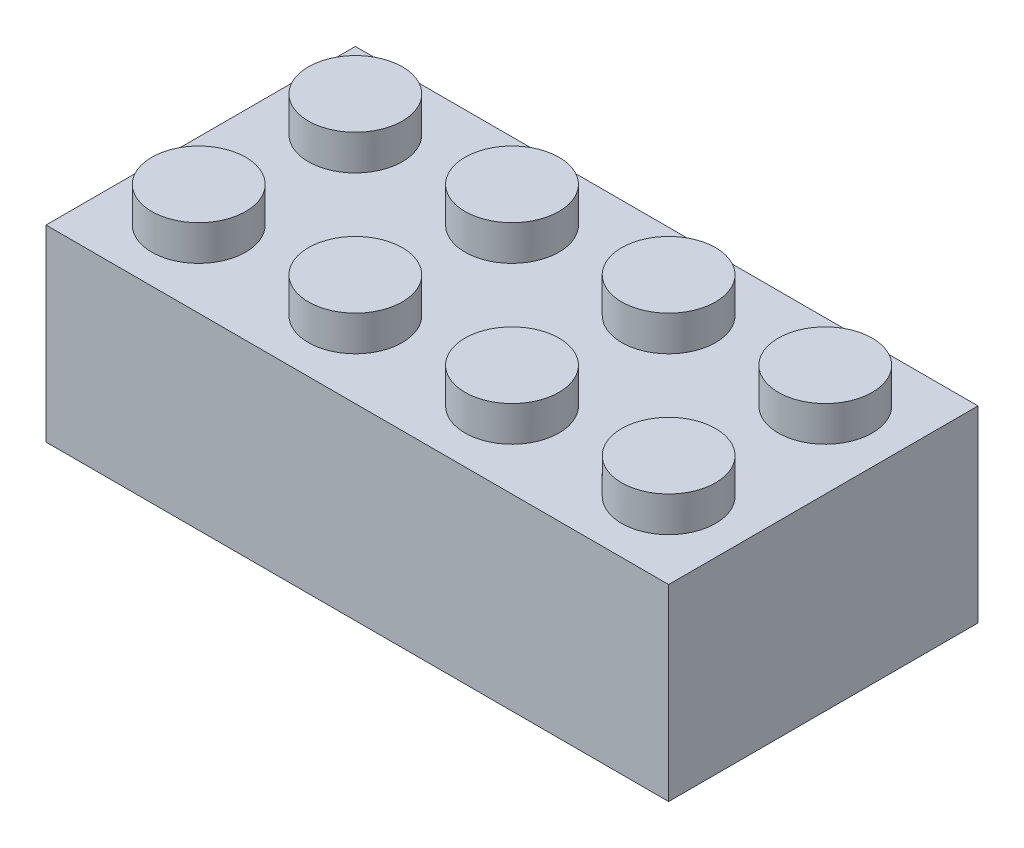
SolidWorks part; units mm, degrees
ref_plane "Front Plane" through (0, 0, 0) normal (0, 0, 1) x (1, 0, 0)
ref_plane "Top Plane" through (0, 0, 0) normal (0, 1, 0) x (1, 0, 0)
ref_plane "Right Plane" through (0, 0, 0) normal (1, 0, 0) x (0, 0, -1)
sketch "Sketch1" plane through (0, 0, 0) normal (0, 1, 0) x (1, 0, 0)
  line L1 (-15.9, -7.9) -> (15.9, -7.9)
  line L2 (-15.9, -7.9) -> (-15.9, 7.9)
  line L3 (-15.9, 7.9) -> (15.9, 7.9)
  line L4 (15.9, -7.9) -> (15.9, 7.9)
  line L5 (-15.9, -7.9) -> (15.9, 7.9) construction
  line L6 (-15.9, 7.9) -> (15.9, -7.9) construction
  point P0 (0, 0)
  dimension "D1" = 31.8
  dimension "D2" = 15.8
extrude "Boss-Extrude1" add sketch "Sketch1" along normal blind 9.6
sketch "Sketch2" plane through (0, 0, 0) normal (0, -1, 0) x (1, 0, 0)
  line L0 (-15.9, 7.9) -> (15.9, 7.9) construction
  line L1 (-14.5, -6.7) -> (14.5, -6.7)
  line L2 (-14.5, -6.7) -> (-14.5, 6.7)
  line L3 (-14.5, 6.7) -> (14.5, 6.7)
  line L4 (14.5, -6.7) -> (14.5, 6.7)
  line L5 (-14.5, -6.7) -> (14.5, 6.7) construction
  line L6 (-14.5, 6.7) -> (14.5, -6.7) construction
  line L7 (-15.9, -7.9) -> (-15.9, 7.9) construction
  point P0 (0, 0)
  dimension "D1" = 1.2
  dimension "D2" = 1.4
extrude "Cut-Extrude1" cut sketch "Sketch2" against normal offset from surface (8.6 mm away) 1 up to face at (0, 9.6, 0)
sketch "Sketch3" plane through (0, 8.6, 0) normal (0, -1, 0) x (1, 0, 0)
  line L0 (0, 0) -> (-14.5, 0) construction
  line L1 (-14.5, -6.7) -> (-14.5, 6.7) construction
  line L2 (0, 0) -> (0, 6.7) construction
  line L3 (-14.5, 6.7) -> (14.5, 6.7) construction
  line L4 (-14.5, 4) -> (0, 4) construction
  line L5 (-4, 6.7) -> (-4, 0) construction
  line L6 (-12, 6.7) -> (-12, 0) construction
  circle A0 centre (-12, 4) radius 2.4
  circle A1 centre (-4, 4) radius 2.4
  circle A2 centre (-12, 4) radius 1.3
  circle A3 centre (-4, 4) radius 1.3
  circle A4 centre (4, 4) radius 1.3
  circle A5 centre (12, 4) radius 1.3
  circle A6 centre (4, 4) radius 2.4
  circle A7 centre (12, 4) radius 2.4
  circle A8 centre (12, -4) radius 2.4
  circle A9 centre (4, -4) radius 2.4
  circle A10 centre (12, -4) radius 1.3
  circle A11 centre (4, -4) radius 1.3
  circle A12 centre (-4, -4) radius 1.3
  circle A13 centre (-12, -4) radius 1.3
  circle A14 centre (-4, -4) radius 2.4
  circle A15 centre (-12, -4) radius 2.4
  dimension "D4" = 4.8
  dimension "D5" = 4.8
  dimension "D6" = 1.1
  dimension "D7" = 1.1
  dimension "D1" = 4
  dimension "D2" = 12
  dimension "D3" = 4
extrude "Boss-Extrude2" add sketch "Sketch3" against normal blind 2.8 contours A15 | A14 | A0 | A1 | A6 | A9 | A7 | A8
extrude "Cut-Extrude2" cut sketch "Sketch3<3>" against normal offset from surface (1.7 mm away) 1.1 contours A13 | A2 | A3 | A12 | A4 | A11 | A10 | A5 up to face at (-12, 11.4, 1.6)
sketch "Sketch3<3>" plane through (0, 8.6, 0) normal (0, -1, 0) x (1, 0, 0) same geometry as "Sketch3"
sketch "Sketch4" plane through (0, 8.6, 0) normal (0, -1, 0) x (1, 0, 0)
  line L0 (-14.5, 0) -> (14.5, 0) construction
  line L1 (-14.5, -6.7) -> (-14.5, 6.7) construction
  line L2 (14.5, -6.7) -> (14.5, 6.7) construction
  circle A0 centre (0, 0) radius 3.25
  circle A1 centre (-8, 0) radius 3.25
  circle A2 centre (8, 0) radius 3.25
  circle A3 centre (-8, 0) radius 2.05
  circle A4 centre (0, 0) radius 2.05
  circle A5 centre (8, 0) radius 2.05
  dimension "D1" = 6.5
  dimension "D2" = 6.5
  dimension "D3" = 6.5
  dimension "D6" = 1.2
  dimension "D7" = 1.2
  dimension "D8" = 1.2
  dimension "D4" = 8
  dimension "D5" = 8
extrude "Boss-Extrude3" add sketch "Sketch4" along normal up to surface (8.6 mm away) up to face at (0, 0, 0)
ref_plane "Plane1" through (0, 2.3, 0) normal (0, 1, 0) x (1, 0, 0)
sketch "Sketch5" plane through (0, 2.3, 0) normal (0, -1, 0) x (1, 0, 0)
  line L0 (0, 3.25) -> (0, 6.7)
  line L1 (14.5, 6.7) -> (-14.5, 6.7) construction
  line L2 (0, -3.25) -> (0, -6.7)
  line L3 (14.5, -6.7) -> (-14.5, -6.7) construction
  circle A0 centre (0, 0) radius 3.25 construction
  circle A1 centre (0, 0) radius 3.25 construction
rib "Rib1" sketch "Sketch5" sketch "Sketch5" thickness 1.1 extrusion direction normal to sketch draft on no parameters "D1"=1.1
sketch "Sketch6" plane through (0, 0, 0) normal (0, -1, 0) x (1, 0, 0)
  line L0 (14.5, 6.7) -> (-14.5, 6.7) construction
  line L1 (-12.6, 6.7) -> (-11.4, 6.7)
  line L2 (-12.6, 6.7) -> (-12.6, 6.5)
  line L3 (-12.6, 6.5) -> (-11.4, 6.5)
  line L4 (-11.4, 6.7) -> (-11.4, 6.5)
  line L5 (0, 9.2782) -> (0, -8.6558) construction
  line L6 (-16.6113, 0) -> (16.4557, 0) construction
  line L7 (-12, 6.7) -> (-12, 0) construction
  line L8 (-8, 0) -> (-8, 6.7) construction
  line L9 (-4.6, 6.7) -> (-4.6, 6.5)
  line L10 (-3.4, 6.5) -> (-4.6, 6.5)
  line L11 (-3.4, 6.7) -> (-3.4, 6.5)
  line L12 (-3.4, 6.7) -> (-4.6, 6.7)
  line L13 (3.4, 6.7) -> (4.6, 6.7)
  line L14 (3.4, 6.7) -> (3.4, 6.5)
  line L15 (3.4, 6.5) -> (4.6, 6.5)
  line L16 (4.6, 6.7) -> (4.6, 6.5)
  line L17 (11.4, 6.7) -> (11.4, 6.5)
  line L18 (12.6, 6.5) -> (11.4, 6.5)
  line L19 (12.6, 6.7) -> (12.6, 6.5)
  line L20 (12.6, 6.7) -> (11.4, 6.7)
  line L21 (12.6, -6.7) -> (11.4, -6.7)
  line L22 (12.6, -6.7) -> (12.6, -6.5)
  line L23 (12.6, -6.5) -> (11.4, -6.5)
  line L24 (11.4, -6.7) -> (11.4, -6.5)
  line L25 (4.6, -6.7) -> (4.6, -6.5)
  line L26 (3.4, -6.5) -> (4.6, -6.5)
  line L27 (3.4, -6.7) -> (3.4, -6.5)
  line L28 (3.4, -6.7) -> (4.6, -6.7)
  line L29 (-3.4, -6.7) -> (-4.6, -6.7)
  line L30 (-3.4, -6.7) -> (-3.4, -6.5)
  line L31 (-3.4, -6.5) -> (-4.6, -6.5)
  line L32 (-4.6, -6.7) -> (-4.6, -6.5)
  line L33 (-11.4, -6.7) -> (-11.4, -6.5)
  line L34 (-12.6, -6.5) -> (-11.4, -6.5)
  line L35 (-12.6, -6.7) -> (-12.6, -6.5)
  line L36 (-12.6, -6.7) -> (-11.4, -6.7)
  line L37 (-14.5, -6.7) -> (-14.5, 6.7) construction
  line L38 (-14.3, -4.6) -> (-14.3, -3.4)
  line L39 (-14.5, 4.6) -> (-14.3, 4.6)
  line L40 (-14.5, 4.6) -> (-14.5, 3.4)
  line L41 (-14.5, 3.4) -> (-14.3, 3.4)
  line L42 (-14.3, 4.6) -> (-14.3, 3.4)
  line L43 (-14.3, 4) -> (-12, 4) construction
  line L44 (-14.5, -3.4) -> (-14.3, -3.4)
  line L45 (-14.5, -4.6) -> (-14.5, -3.4)
  line L46 (-14.5, -4.6) -> (-14.3, -4.6)
  line L47 (14.5, -4.6) -> (14.3, -4.6)
  line L48 (14.5, -4.6) -> (14.5, -3.4)
  line L49 (14.5, -3.4) -> (14.3, -3.4)
  line L50 (14.3, 4.6) -> (14.3, 3.4)
  line L51 (14.5, 3.4) -> (14.3, 3.4)
  line L52 (14.5, 4.6) -> (14.5, 3.4)
  line L53 (14.5, 4.6) -> (14.3, 4.6)
  line L54 (14.3, -4.6) -> (14.3, -3.4)
  point P54 (0, 0)
  dimension "D1" = 4
  dimension "D2" = 1.2
  dimension "D3" = 0.2
  dimension "D4" = 1.2
  dimension "D5" = 0.2
  dimension "D6" = 4
extrude "Boss-Extrude4" add sketch "Sketch6" against normal up to surface (8.6 mm away) up to face at (-4, 8.6, 2.7)
